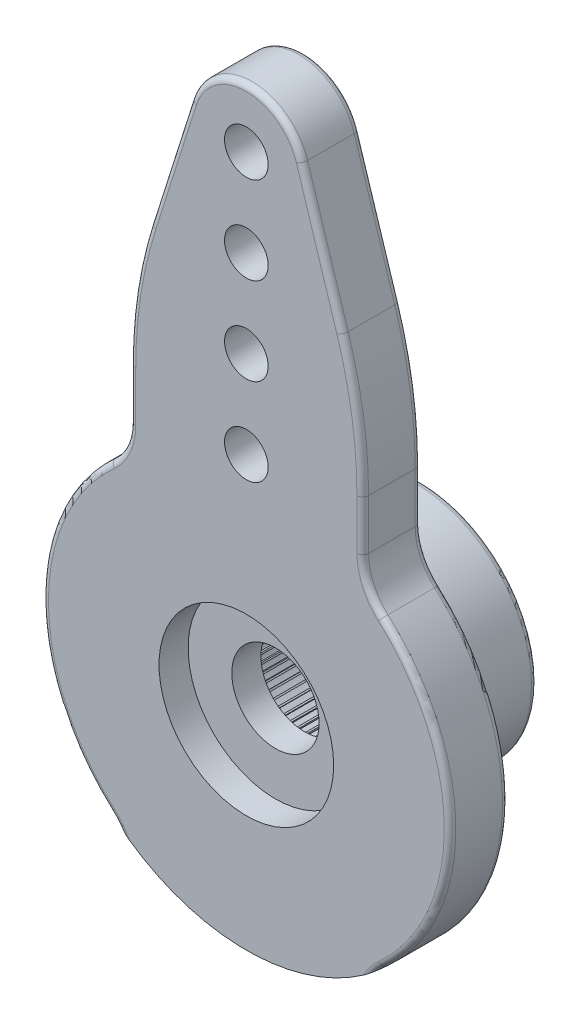
SolidWorks part; units mm, degrees
ref_plane "Ön Düzlem" through (0, 0, 0) normal (0, 0, 1) x (1, 0, 0)
ref_plane "Üst Düzlem" through (0, 0, 0) normal (0, 1, 0) x (1, 0, 0)
ref_plane "Sağ Düzlem" through (0, 0, 0) normal (1, 0, 0) x (0, 0, -1)
sketch "Sketch1" plane through (0, 0, 0) normal (0, 0, 1) x (1, 0, 0)
  line L0 (-4, 10.7446) -> (-4, 5.7446)
  line L1 (4, 10.7446) -> (4, 5.7446)
  line L2 (0, 0) -> (0, 16.75) construction
  line L3 (-4, 5.7446) -> (4, 5.7446) construction
  line L4 (-1.9067, 17.3539) -> (-4, 10.7446)
  line L5 (1.9067, 17.3539) -> (4, 10.7446)
  circle A0 centre (0, 0) radius 7
  circle A1 centre (0, 0) radius 18.75
  circle A2 centre (0, 16.75) radius 2
  circle A3 centre (0, 0) radius 1.5
  dimension "D1" = 37.5
  dimension "D2" = 14
  dimension "D3" = 4
  dimension "D5" = 3
  dimension "D4" = 5
  dimension "D6" = 8
extrude "Boss-Extrude1" add sketch "Sketch1" along normal blind 2 contours A0 A3 | A2 L4 L0 A0 L1 L5 | A2 region at (0, 10.6981, 0) region at (0, 6.802, 0) region at (0, 16.75, 0)
fillet "Fillet1" radius 15 2 edges at (-4, 10.7446, 1) (4, 10.7446, 1)
sketch "Sketch2" plane through (0, 0, 2) normal (0, 0, 1) x (1, 0, 0)
  line L0 (0, 0) -> (0, 18.75) construction
  arc A0 (1.9067, 17.3539) -> (-1.9067, 17.3539) centre (0, 16.75) ccw construction
  circle A1 centre (0, 16.75) radius 0.75
  circle A2 centre (0, 13.75) radius 0.75
  circle A3 centre (0, 10.75) radius 0.75
  circle A4 centre (0, 7.75) radius 0.75
  dimension "D1" = 1.5
  dimension "D2" = 2
  dimension "D3" = 4
extrude "Cut-Extrude1" cut sketch "Sketch2" against normal through all
pattern_circular "CirPattern2" count 2 over 360 about axis through (0, 0, 2) along (0, 0, 1) of "Boss-Extrude1", "Fillet1", "Cut-Extrude1"
fillet "Fillet2" radius 2 4 edges at (4, 5.7446, 1) (-4, 5.7446, 1) (-4, -5.7446, 1) (4, -5.7446, 1)
sketch "Sketch3" plane through (0, 0, 2) normal (0, 0, 1) x (1, 0, 0)
  circle A0 centre (0, 0) radius 3
  dimension "D1" = 6
extrude "Cut-Extrude2" cut sketch "Sketch3" against normal blind 1
sketch "Sketch4" plane through (0, 0, 0) normal (0, 0, -1) x (-1, 0, 0)
  circle A0 centre (0, 0) radius 4
  circle A1 centre (0, 0) radius 3
  dimension "D1" = 8
  dimension "D2" = 6
extrude "Boss-Extrude2" add sketch "Sketch4" along normal blind 4
sketch "Sketch5" plane through (0, 0, -4) normal (0, 0, -1) x (-1, 0, 0)
  line L0 (0, 0) -> (0, -4) construction
  line L2 (0.025, -2.8941) -> (-0.025, -2.8941)
  line L3 (0.025, -2.8941) -> (0.025, -3.3941)
  line L4 (0.025, -3.3941) -> (-0.025, -3.3941)
  line L5 (-0.025, -2.8941) -> (-0.025, -3.3941)
  line L6 (0.025, -2.8941) -> (-0.025, -3.3941) construction
  line L7 (0.025, -3.3941) -> (-0.025, -2.8941) construction
  circle A1 centre (0, 0) radius 4 construction
  point P0 (0, -3.1441)
  dimension "D1" = 0.05
  dimension "D2" = 0.5
extrude "Boss-Extrude3" add sketch "Sketch5" against normal up to surface (4 mm away) up to face at (-3, 0, 0)
pattern_circular "CirPattern3" count 80 over 360 about axis through (0, 0, -4) along (0, 0, -1) of "Boss-Extrude3"
fillet "Fillet3" radius 0.2 42 edges at (0, 18.75, 0) (-2.6033, 15.1545, 0) (-3.8239, 10.7173, 0) (-4, 7.567, 0) (-4.1743, 5.8917, 0) (-7, 0, 0) (-4.1743, -5.8917, 0) (-4, -7.567, 0) (-3.8239, -10.7173, 0) (-2.6033, -15.1545, 0) (0, -18.75, 0) (2.6033, -15.1545, 0) (3.8239, -10.7173, 0) (4, -7.567, 0) (4.1743, -5.8917, 0) (7, 0, 0) (4.1743, 5.8917, 0) (4, 7.567, 0) (3.8239, 10.7173, 0) (0, 18.75, 2) (-2.6033, 15.1545, 2) (-3.8239, 10.7173, 2) (-4, 7.567, 2) (-4.1743, 5.8917, 2) (-7, 0, 2) (-4.1743, -5.8917, 2) (-4, -7.567, 2) (-3.8239, -10.7173, 2) (-2.6033, -15.1545, 2) (0, -18.75, 2) (2.6033, -15.1545, 2) (3.8239, -10.7173, 2) (4, -7.567, 2) (4.1743, -5.8917, 2) (7, 0, 2) (4.1743, 5.8917, 2) (4, 7.567, 2) (3.8239, 10.7173, 2) (2.6033, 15.1545, 0) (2.6033, 15.1545, 2) (4, 0, 0) (-4, 0, -4)
sketch "Esquisse1" plane through (0, 0, 2) normal (0, 0, 1) x (1, 0, 0)
  line L0 (-4.6667, -5.2175) -> (-3.9258, -21.0317)
  line L1 (-3.9258, -21.0317) -> (5.2011, -20.6041)
  line L2 (5.2011, -20.6041) -> (4.7267, -5.1632)
  arc A0 (-4.6667, 5.2175) -> (-4.6667, -5.2175) centre (0, 0) ccw construction
  arc A1 (-4.6667, 5.2175) -> (-4.6667, -5.2175) centre (0, 0) ccw
  arc A2 (4.6667, -5.2175) -> (4.6667, 5.2175) centre (0, 0) ccw construction
  arc A3 (4.6667, -5.2175) -> (4.6667, 5.2175) centre (0, 0) ccw
  arc A4 (-4.6667, -5.2175) -> (4.7267, -5.1632) centre (0, 0) ccw
extrude "Enlèv. mat.-Extru.1" cut sketch "Esquisse1" against normal through all contours L0 L1 L2 A4
sketch "Sketch6" plane through (0, 0, 2) normal (0, 0, 1) x (1, 0, 0)
  line L4 (3.8, 6.7082) -> (3.8, 8.4259)
  line L5 (3.1092, 12.8946) -> (1.716, 17.2935)
  line L6 (-1.716, 17.2935) -> (-3.1092, 12.8946)
  line L7 (-3.8, 8.4259) -> (-3.8, 6.7082)
  line L8 (3.8, 6.7082) -> (3.8, 8.4259)
  line L9 (3.1092, 12.8946) -> (1.716, 17.2935)
  line L10 (-1.716, 17.2935) -> (-3.1092, 12.8946)
  line L11 (-3.8, 8.4259) -> (-3.8, 6.7082)
  circle A0 centre (0, 16.75) radius 0.75 construction
  circle A1 centre (0, 13.75) radius 0.75 construction
  circle A2 centre (0, 10.75) radius 0.75 construction
  circle A3 centre (0, 7.75) radius 0.75 construction
  circle A4 centre (0, 0) radius 1.5 construction
  circle A5 centre (0, 16.75) radius 0.75
  circle A6 centre (0, 13.75) radius 0.75
  circle A7 centre (0, 10.75) radius 0.75
  circle A8 centre (0, 7.75) radius 0.75
  circle A9 centre (0, 0) radius 1.5
  arc A10 (-4.0341, -5.7207) -> (-4.5333, -5.0684) centre (-6, -6.7082) ccw
  arc A11 (-4.0341, -5.7207) -> (4.0341, -5.7207) centre (0, 0) ccw
  arc A12 (4.5333, -5.0684) -> (4.0341, -5.7207) centre (6, -6.7082) ccw
  arc A13 (4.5333, -5.0684) -> (4.5333, 5.0684) centre (0, 0) ccw
  arc A14 (3.8, 6.7082) -> (4.5333, 5.0684) centre (6, 6.7082) ccw
  arc A15 (3.8, 8.4259) -> (3.1092, 12.8946) centre (-11, 8.4259) ccw
  arc A16 (1.716, 17.2935) -> (-1.716, 17.2935) centre (0, 16.75) ccw
  arc A17 (-3.1092, 12.8946) -> (-3.8, 8.4259) centre (11, 8.4259) ccw
  arc A18 (-4.5333, 5.0684) -> (-3.8, 6.7082) centre (-6, 6.7082) ccw
  arc A19 (-4.5333, 5.0684) -> (-4.5333, -5.0684) centre (0, 0) ccw
  arc A20 (-4.0341, -5.7207) -> (-4.5333, -5.0684) centre (-6, -6.7082) ccw
  arc A21 (-4.0341, -5.7207) -> (4.0341, -5.7207) centre (0, 0) ccw
  arc A22 (4.5333, -5.0684) -> (4.0341, -5.7207) centre (6, -6.7082) ccw
  arc A23 (4.5333, -5.0684) -> (4.5333, 5.0684) centre (0, 0) ccw
  arc A24 (3.8, 6.7082) -> (4.5333, 5.0684) centre (6, 6.7082) ccw
  arc A25 (3.8, 8.4259) -> (3.1092, 12.8946) centre (-11, 8.4259) ccw
  arc A26 (1.716, 17.2935) -> (-1.716, 17.2935) centre (0, 16.75) ccw
  arc A27 (-3.1092, 12.8946) -> (-3.8, 8.4259) centre (11, 8.4259) ccw
  arc A28 (-4.5333, 5.0684) -> (-3.8, 6.7082) centre (-6, 6.7082) ccw
  arc A29 (-4.5333, 5.0684) -> (-4.5333, -5.0684) centre (0, 0) ccw
  dimension "D1" = 0
